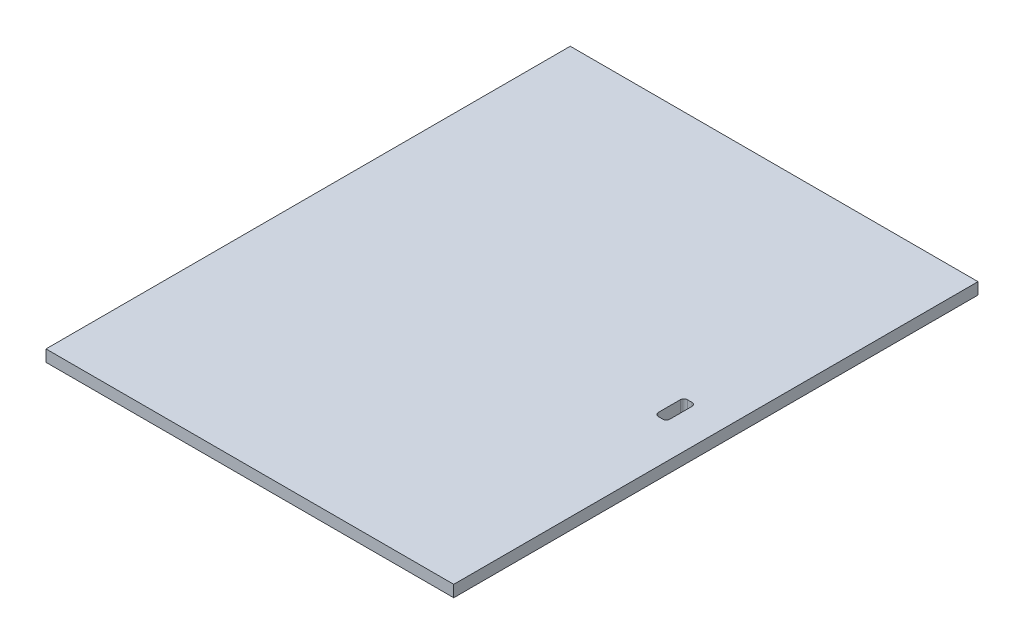
SolidWorks part; units mm, degrees
ref_plane "前视基准面" through (0, 0, 0) normal (0, 0, 1) x (1, 0, 0)
ref_plane "上视基准面" through (0, 0, 0) normal (0, 1, 0) x (1, 0, 0)
ref_plane "右视基准面" through (0, 0, 0) normal (1, 0, 0) x (0, 0, -1)
other "Configuration Table"
sketch "草图1" plane through (0, 0, 0) normal (0, 1, 0) x (1, 0, 0)
  line L1 (0, 0) -> (700, 0)
  line L2 (0, 0) -> (0, 900)
  line L3 (0, 900) -> (700, 900)
  line L4 (700, 0) -> (700, 900)
  dimension "D1" = 700
  dimension "D2" = 900
extrude "凸台-拉伸1" add sketch "草图1" along normal blind 20
sketch "草图2" plane through (0, 20, 0) normal (0, 1, 0) x (1, 0, 0)
  line L0 (700, 0) -> (700, 900) construction
  line L1 (626, 475) -> (634, 475)
  line L2 (620, 469) -> (620, 431)
  line L3 (626, 425) -> (634, 425)
  line L4 (640, 469) -> (640, 431)
  arc A0 (634, 425) -> (640, 431) centre (634, 431) ccw
  arc A1 (634, 475) -> (640, 469) centre (634, 469) cw
  arc A2 (626, 475) -> (620, 469) centre (626, 469) ccw
  arc A3 (620, 431) -> (626, 425) centre (626, 431) ccw
  point P6 (640, 425)
  point P9 (640, 475)
  point P12 (620, 475)
  point P17 (640, 450)
  point P18 (700, 450)
  dimension "D3" = 6
  dimension "D1" = 20
  dimension "D2" = 50
  dimension "D4" = 60
  dimension "D5" = 0
extrude "切除-拉伸1" cut sketch "草图2" against normal blind 20
